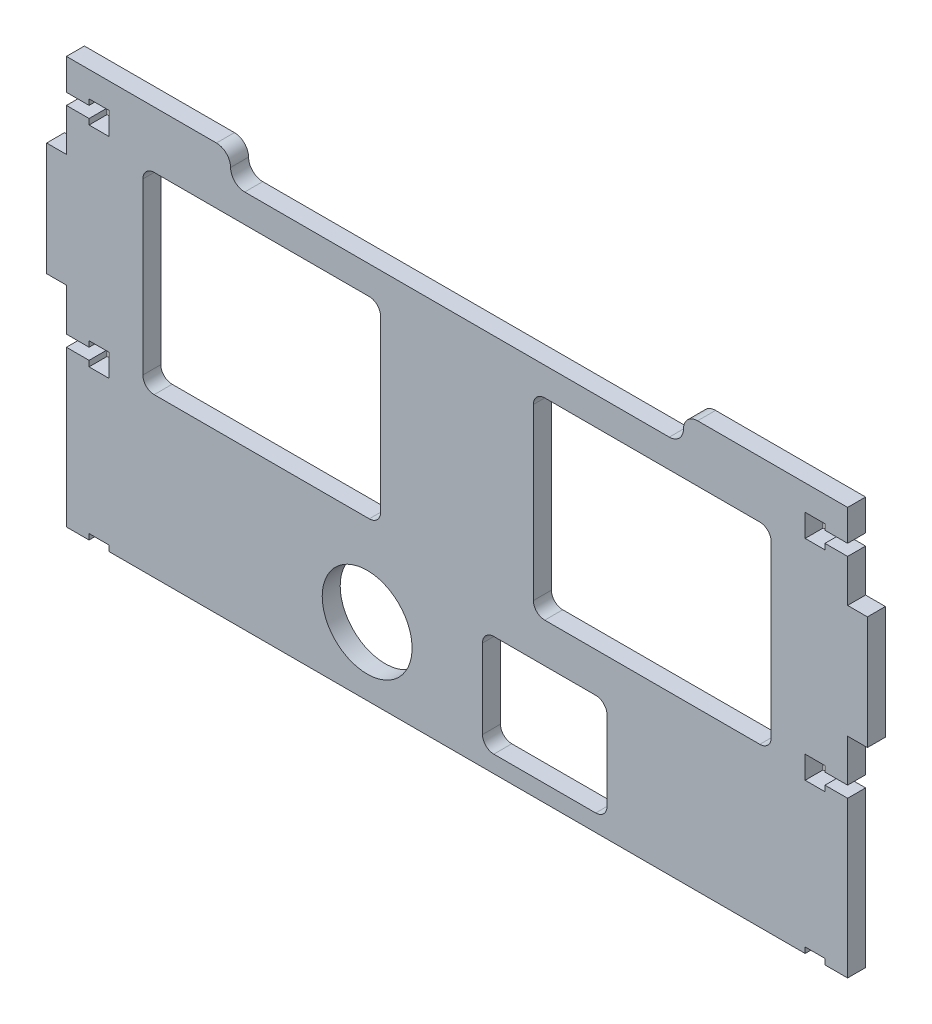
SolidWorks part; units mm, degrees
ref_plane "Front Plane" through (0, 0, 0) normal (0, 0, 1) x (1, 0, 0)
ref_plane "Top Plane" through (0, 0, 0) normal (0, 1, 0) x (1, 0, 0)
ref_plane "Right Plane" through (0, 0, 0) normal (1, 0, 0) x (0, 0, -1)
sketch "Sketch1" plane through (0, 0, 0) normal (0, 0, 1) x (1, 0, 0)
  line L0 (-69, -10) -> (-69, -38)
  line L5 (-69, 25) -> (69, 25)
  line L6 (-69, 25) -> (-69, 10)
  line L7 (-69, -38) -> (69, -38)
  line L8 (69, 25) -> (69, 10)
  line L9 (-69, -10) -> (-72.5, -10)
  line L11 (-69, 10) -> (-72.5, 10)
  line L12 (-72.5, -10) -> (-72.5, 10)
  line L13 (69, 10) -> (72.5, 10)
  line L15 (69, -10) -> (72.5, -10)
  line L16 (72.5, 10) -> (72.5, -10)
  line L17 (69, -10) -> (69, -38)
  point P13 (-72.5, 0)
  point P14 (72.5, 0)
  dimension "D1" = 63
  dimension "D2" = 138
  dimension "D3" = 69
  dimension "D4" = 25
  dimension "D5" = 20
  dimension "D6" = 3.5
  dimension "D7" = 0
  dimension "D8" = 20
  dimension "D9" = 3.5
  dimension "D10" = 0
extrude "Boss-Extrude1" add sketch "Sketch1" against normal blind 3.175
sketch "Sketch2" plane through (0, 0, 0) normal (0, 0, 1) x (1, 0, 0)
  line L0 (-69, 19.5) -> (-65, 19.5)
  line L2 (-65, 19.5) -> (-65, 20.5)
  line L3 (-65, 20.5) -> (-61.5, 20.5)
  line L4 (-61.5, 20.5) -> (-61.5, 16.5)
  line L5 (-61.5, 16.5) -> (-65, 16.5)
  line L6 (-65, 16.5) -> (-65, 17.5)
  line L7 (-65, 17.5) -> (-69, 17.5)
  line L8 (-69, 17.5) -> (-69, 19.5)
  line L10 (-69, 25) -> (-69, 10) construction
  point P2 (-69, 18.5)
  dimension "D1" = 4
  dimension "D2" = 3.5
  dimension "D3" = 2
  dimension "D4" = 2
  dimension "D5" = 3.5
  dimension "D6" = 7.5
  dimension "D7" = 18.5
  dimension "D8" = 0
extrude "Cut-Extrude1" cut sketch "Sketch2" against normal through all both and the other way through all
ref_plane "Plane3" through (0, 0, 0) normal (0, 1, 0) x (1, 0, 0)
ref_plane "Plane4" through (0, 0, 0) normal (-1, 0, 0) x (0, 0, 1)
mirror "Mirror1" about plane through (0, 0, 0) normal (-1, 0, 0) of "Cut-Extrude1"
mirror "Mirror2" about plane through (0, 0, 0) normal (0, 1, 0) of "Mirror1", "Cut-Extrude1"
sketch "Sketch4" plane through (0, 0, 0) normal (0, 0, 1) x (1, 0, 0)
  line L0 (69, -38) -> (69, -19.5) construction
  line L1 (-69, -38) -> (69, -38)
  line L2 (-69, -38) -> (-69, -47)
  line L3 (-69, -47) -> (69, -47)
  line L4 (69, -38) -> (69, -47)
  line L5 (-69, -19.5) -> (-69, -38) construction
  line L6 (-69, -38) -> (69, -38) construction
  dimension "D1" = 9
  dimension "D2" = 0
  dimension "D3" = 0
  dimension "D4" = 0
extrude "Boss-Extrude3" add sketch "Sketch4" against normal up to surface (3.175 mm away) up to face at (0, -0.5909, -3.175)
sketch "Sketch5" plane through (0, 0, 0) normal (0, 0, 1) x (1, 0, 0)
  line L0 (69, 25) -> (-69, 25) construction
  line L1 (-40, 25) -> (40, 25)
  line L2 (-40, 25) -> (-40, 20)
  line L3 (-40, 20) -> (40, 20)
  line L4 (40, 25) -> (40, 20)
  point P4 (0, 25)
  point P7 (0, 25)
  dimension "D1" = 80
  dimension "D2" = 0
  dimension "D3" = 0
  dimension "D4" = 5
extrude "Cut-Extrude2" cut sketch "Sketch5" against normal through all both and the other way through all
fillet "Fillet1" radius 2.5 4 edges at (40, 20, -1.5875) (40, 25, -1.5875) (-40, 20, -1.5875) (-40, 25, -1.5875)
sketch "Sketch6" plane through (0, 0, 0) normal (0, 0, 1) x (1, 0, 0)
  line L0 (-69, -47) -> (69, -47) construction
  line L1 (61.5, -47) -> (65, -47)
  line L2 (61.5, -47) -> (61.5, -46)
  line L3 (61.5, -46) -> (65, -46)
  line L4 (65, -47) -> (65, -46)
  line L5 (65, -19.5) -> (65, -20.5) construction
  line L6 (61.5, -20.5) -> (61.5, -16.5) construction
  dimension "D1" = 0
  dimension "D2" = 0
  dimension "D3" = 1
extrude "Cut-Extrude3" cut sketch "Sketch6" against normal through all both and the other way through all
mirror "Mirror3" about plane through (0, 0, 0) normal (-1, 0, 0) of "Cut-Extrude3"
sketch "Sketch10" plane through (0, 0, -3.175) normal (0, 0, -1) x (-1, 0, 0)
  line L1 (55.5, -19) -> (13.5, -19)
  line L2 (55.5, -19) -> (55.5, 15)
  line L3 (55.5, 15) -> (13.5, 15)
  line L4 (13.5, -19) -> (13.5, 15)
  line L6 (61.5, 16.5) -> (61.5, 20.5) construction
  line L8 (37.5, 20) -> (-37.5, 20) construction
  dimension "D1" = 6
  dimension "D2" = 34
  dimension "D3" = 13.5
  dimension "D4" = 5
extrude "Cut-Extrude4" cut sketch "Sketch10" against normal through all
fillet "Fillet2" radius 2 4 edges at (-13.5, 15, -1.5875) (-55.5, 15, -1.5875) (-13.5, -19, -1.5875) (-55.5, -19, -1.5875)
mirror "Mirror4" about plane through (0, 0, 0) normal (-1, 0, 0) of "Cut-Extrude4", "Fillet2"
sketch "Sketch11" plane through (0, 0, -3.175) normal (0, 0, -1) x (-1, 0, 0)
  line L0 (-69, 25) -> (-42.5, 25) construction
  circle A0 centre (15.875, -35) radius 7.9375
  dimension "D1" = 15.875
  dimension "D2" = 15.875
  dimension "D3" = 60
extrude "Cut-Extrude5" cut sketch "Sketch11" against normal blind 10
sketch "Sketch12" plane through (0, 0, -3.175) normal (0, 0, -1) x (-1, 0, 0)
  line L0 (-13.5, 13) -> (-13.5, -17) construction
  line L1 (-4.5, -44) -> (-26.5, -44)
  line L2 (-4.5, -44) -> (-4.5, -26)
  line L3 (-4.5, -26) -> (-26.5, -26)
  line L4 (-26.5, -44) -> (-26.5, -26)
  line L5 (-15.5, -19) -> (-53.5, -19) construction
  line L6 (61.5, -47) -> (-61.5, -47) construction
  dimension "D1" = 9
  dimension "D2" = 7
  dimension "D3" = 3
  dimension "D4" = 22
extrude "Cut-Extrude6" cut sketch "Sketch12" against normal blind 10
fillet "Fillet3" radius 2 4 edges at (26.5, -26, -1.5875) (4.5, -26, -1.5875) (26.5, -44, -1.5875) (4.5, -44, -1.5875)
